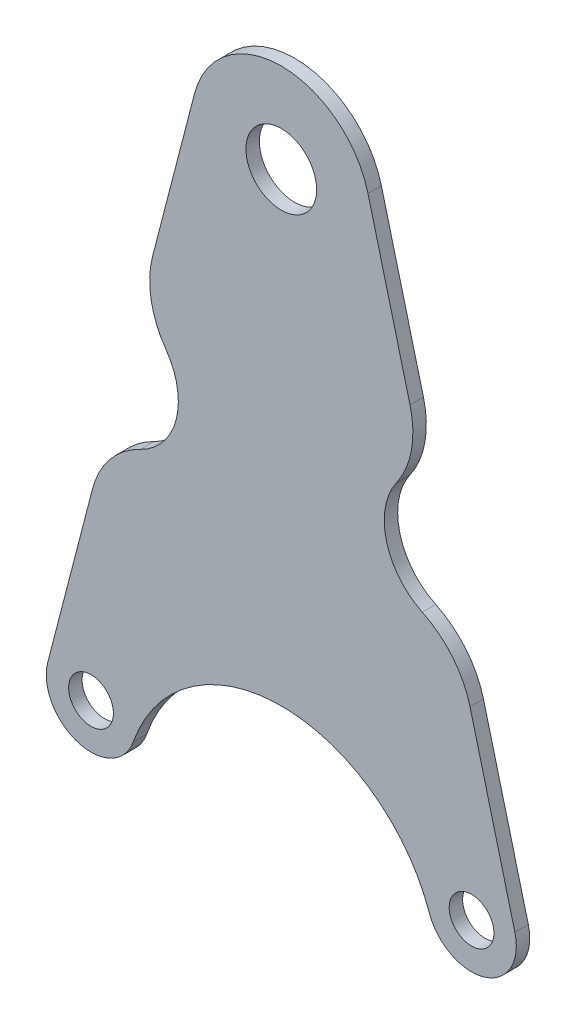
SolidWorks part; units mm, degrees
ref_plane "Спереди" through (0, 0, 0) normal (0, 0, 1) x (1, 0, 0)
ref_plane "Сверху" through (0, 0, 0) normal (0, 1, 0) x (1, 0, 0)
ref_plane "Справа" through (0, 0, 0) normal (1, 0, 0) x (0, 0, -1)
sketch "Эскиз1" plane through (0, 0, 0) normal (0, 0, 1) x (1, 0, 0)
  line L0 (0, 20) -> (0, -181.3933) construction
  line L6 (-19.3591, 5.0223) -> (-52.1796, -121.4889)
  line L8 (19.3591, 5.0223) -> (52.1796, -121.4889)
  circle A0 centre (0, 0) radius 7.9
  circle A1 centre (-42.5, -124) radius 5
  arc A2 (-19.3591, 5.0223) -> (19.3591, 5.0223) centre (0, 0) cw
  arc A3 (-52.1796, -121.4889) -> (-33.0556, -127.2867) centre (-42.5, -124) ccw
  circle A5 centre (42.5, -124) radius 5
  arc A6 (52.1796, -121.4889) -> (33.0556, -127.2867) centre (42.5, -124) cw
  arc A8 (-33.0556, -127.2867) -> (33.0556, -127.2867) centre (0, -138.7902) cw
  point P8 (0, -134)
  point P19 (0, -134)
  dimension "D1" = 15.8
  dimension "D4" = 20
  dimension "D6" = 10
  dimension "D5" = 10
  dimension "D7" = 35
  dimension "D2" = 85
  dimension "D3" = 124
extrude "Бобышка-Вытянуть1" add sketch "Эскиз1" along normal blind 3
sketch "Эскиз2" plane through (0, 0, 3) normal (0, 0, 1) x (1, 0, 0)
  line L0 (0, -16) -> (0, -54) construction
  line L1 (8.05, -16) -> (8.05, -54) construction
  line L2 (-8.05, -16) -> (-8.05, -54) construction
  line L3 (4, -34.05) -> (-4, -34.05)
  line L4 (0, 0) -> (0, -65.5898) construction
  arc A3 (8.05, -16) -> (-8.05, -16) centre (0, -16) ccw construction
  arc A8 (8.05, -16) -> (9.8293, -20.4483) centre (14.5, -16) ccw
  arc A9 (-8.05, -54) -> (8.05, -54) centre (0, -54) ccw construction
  arc A10 (9.8293, -20.4483) -> (4, -34.05) centre (4, -26) cw
  arc A11 (8.05, -16) -> (-8.05, -16) centre (0, -16) ccw
  arc A12 (-9.8293, -20.4483) -> (-4, -34.05) centre (-4, -26) ccw
  arc A13 (-8.05, -16) -> (-9.8293, -20.4483) centre (-14.5, -16) cw
  point P8 (0, -35)
  point P20 (0, -34.05)
  dimension "D1" = 16
  dimension "D2" = 8.05
  dimension "D4" = 16.1
  dimension "D7" = 38
  dimension "D3" = 8
  dimension "D5" = 26
extrude "Вырез-Вытянуть1" [suppressed] cut sketch "Эскиз2" against normal blind 4.5
sketch "Эскиз3" plane through (0, 0, 3) normal (0, 0, 1) x (1, 0, 0)
  line L0 (0, 0) -> (0, -88.8714) construction
  circle A0 centre (-38, -56.3915) radius 15
  circle A1 centre (38, -56.3915) radius 15
  circle A2 centre (0, -37.4415) radius 5 construction
  dimension "D1" = 68
  dimension "D2" = 30
  dimension "D4" = 10
  dimension "D3" = 38
extrude "Вырез-Вытянуть2" cut sketch "Эскиз3" against normal through all
fillet "Скругление1" radius 20 4 edges at (39.1711, -71.3457, 1.5) (31.7536, -42.7539, 1.5) (-39.1711, -71.3457, 1.5) (-31.7536, -42.7539, 1.5)
